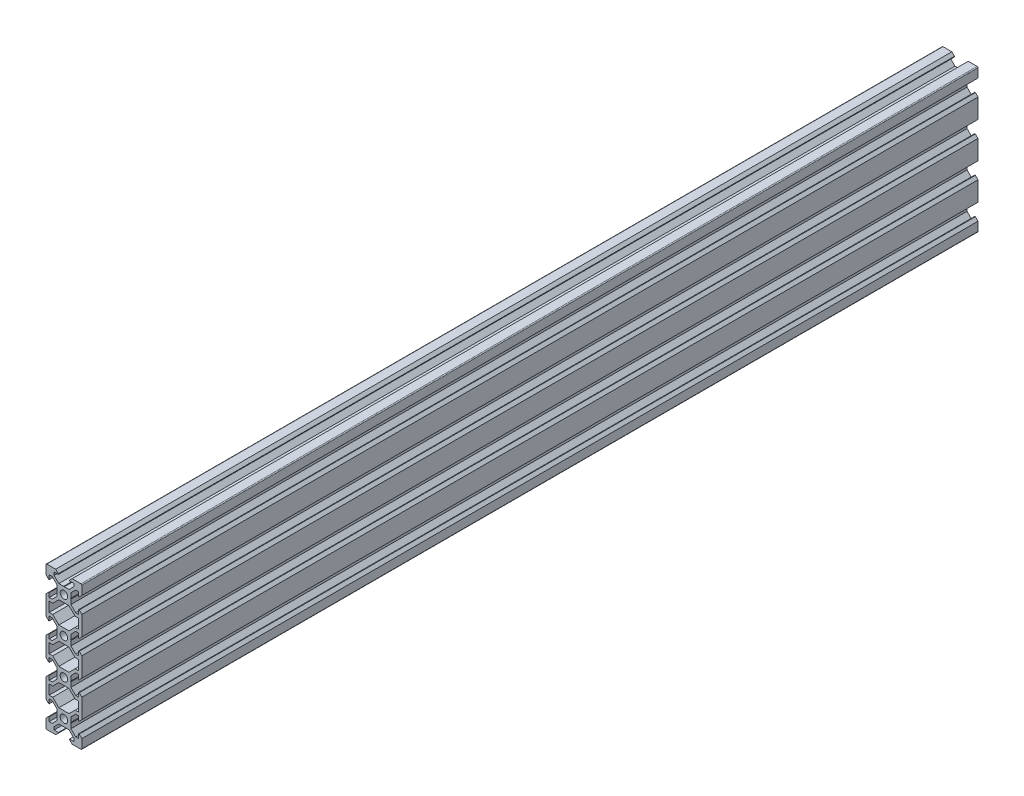
SolidWorks part; units mm, degrees
material "6061-T6 (SS)"
ref_plane "Front Plane" through (0, 0, 0) normal (0, 0, 1) x (1, 0, 0)
ref_plane "Top Plane" through (0, 0, 0) normal (0, 1, 0) x (1, 0, 0)
ref_plane "Right Plane" through (0, 0, 0) normal (1, 0, 0) x (0, 0, -1)
sketch "Sketch1" plane through (0, 0, 0) normal (0, 0, 1) x (1, 0, 0)
  line L0 (0, 0) -> (10, 0) construction
  line L1 (9.5, -40) -> (-9.5, -40)
  line L2 (10, -39.5) -> (10, 39.5)
  line L3 (9.5, 40) -> (-9.5, 40)
  line L4 (-10, -39.5) -> (-10, 39.5)
  line L5 (10, -40) -> (-10, 40) construction
  line L6 (10, 40) -> (-10, -40) construction
  circle A0 centre (0, 30) radius 2.1
  circle A1 centre (0, 10) radius 2.1
  circle A2 centre (0, -10) radius 2.1
  circle A3 centre (0, -30) radius 2.1
  arc A4 (-9.5, -40) -> (-10, -39.5) centre (-9.5, -39.5) cw
  arc A5 (9.5, -40) -> (10, -39.5) centre (9.5, -39.5) ccw
  arc A6 (10, 39.5) -> (9.5, 40) centre (9.5, 39.5) ccw
  arc A7 (-9.5, 40) -> (-10, 39.5) centre (-9.5, 39.5) ccw
  point P0 (0, 0)
  line B0 (0, 30) -> (0, 40) construction
  line B1 (0, 33.69) -> (-0.21, 33.9)
  line B2 (-0.21, 33.9) -> (-2.8393, 33.9)
  line B3 (-2.8393, 33.9) -> (-5.5, 36.5607)
  line B4 (-5.5, 36.5607) -> (-5.5, 38.2)
  line B5 (-5.5, 38.2) -> (-3.125, 38.2)
  line B6 (-3.125, 38.2) -> (-3.125, 38.545)
  line B7 (-3.125, 38.545) -> (-4.58, 40)
  line B8 (-4.58, 40) -> (4.58, 40)
  line B9 (0, 30) -> (-5.9132, 35.9132) construction
  line B10 (3.125, 38.545) -> (4.58, 40)
  line B11 (3.125, 38.2) -> (3.125, 38.545)
  line B12 (5.5, 38.2) -> (3.125, 38.2)
  line B13 (5.5, 36.5607) -> (5.5, 38.2)
  line B14 (2.8393, 33.9) -> (5.5, 36.5607)
  line B15 (0.21, 33.9) -> (2.8393, 33.9)
  line B16 (0, 33.69) -> (0.21, 33.9)
  line B17 (0, 30) -> (-10, 30) construction
  line B18 (-3.69, 30) -> (-3.9, 29.79)
  line B19 (-3.9, 29.79) -> (-3.9, 27.1607)
  line B20 (-3.9, 27.1607) -> (-6.5607, 24.5)
  line B21 (-6.5607, 24.5) -> (-8.2, 24.5)
  line B22 (-8.2, 24.5) -> (-8.2, 26.875)
  line B23 (-8.2, 26.875) -> (-8.545, 26.875)
  line B24 (-8.545, 26.875) -> (-10, 25.42)
  line B25 (-10, 25.42) -> (-10, 34.58)
  line B26 (0, 30) -> (-5.9132, 24.0868) construction
  line B27 (-8.545, 33.125) -> (-10, 34.58)
  line B28 (-8.2, 33.125) -> (-8.545, 33.125)
  line B29 (-8.2, 35.5) -> (-8.2, 33.125)
  line B30 (-6.5607, 35.5) -> (-8.2, 35.5)
  line B31 (-3.9, 32.8393) -> (-6.5607, 35.5)
  line B32 (-3.9, 30.21) -> (-3.9, 32.8393)
  line B33 (-3.69, 30) -> (-3.9, 30.21)
  line B34 (0, 10) -> (-10, 10) construction
  line B35 (-3.69, 10) -> (-3.9, 9.79)
  line B36 (-3.9, 9.79) -> (-3.9, 7.1607)
  line B37 (-3.9, 7.1607) -> (-6.5607, 4.5)
  line B38 (-6.5607, 4.5) -> (-8.2, 4.5)
  line B39 (-8.2, 4.5) -> (-8.2, 6.875)
  line B40 (-8.2, 6.875) -> (-8.545, 6.875)
  line B41 (-8.545, 6.875) -> (-10, 5.42)
  line B42 (-10, 5.42) -> (-10, 14.58)
  line B43 (0, 10) -> (-5.9132, 4.0868) construction
  line B44 (-8.545, 13.125) -> (-10, 14.58)
  line B45 (-8.2, 13.125) -> (-8.545, 13.125)
  line B46 (-8.2, 15.5) -> (-8.2, 13.125)
  line B47 (-6.5607, 15.5) -> (-8.2, 15.5)
  line B48 (-3.9, 12.8393) -> (-6.5607, 15.5)
  line B49 (-3.9, 10.21) -> (-3.9, 12.8393)
  line B50 (-3.69, 10) -> (-3.9, 10.21)
  line B51 (0, -10) -> (-10, -10) construction
  line B52 (-3.69, -10) -> (-3.9, -10.21)
  line B53 (-3.9, -10.21) -> (-3.9, -12.8393)
  line B54 (-3.9, -12.8393) -> (-6.5607, -15.5)
  line B55 (-6.5607, -15.5) -> (-8.2, -15.5)
  line B56 (-8.2, -15.5) -> (-8.2, -13.125)
  line B57 (-8.2, -13.125) -> (-8.545, -13.125)
  line B58 (-8.545, -13.125) -> (-10, -14.58)
  line B59 (-10, -14.58) -> (-10, -5.42)
  line B60 (0, -10) -> (-5.9132, -15.9132) construction
  line B61 (-8.545, -6.875) -> (-10, -5.42)
  line B62 (-8.2, -6.875) -> (-8.545, -6.875)
  line B63 (-8.2, -4.5) -> (-8.2, -6.875)
  line B64 (-6.5607, -4.5) -> (-8.2, -4.5)
  line B65 (-3.9, -7.1607) -> (-6.5607, -4.5)
  line B66 (-3.9, -9.79) -> (-3.9, -7.1607)
  line B67 (-3.69, -10) -> (-3.9, -9.79)
  line B68 (0, -30) -> (-10, -30) construction
  line B69 (-3.69, -30) -> (-3.9, -30.21)
  line B70 (-3.9, -30.21) -> (-3.9, -32.8393)
  line B71 (-3.9, -32.8393) -> (-6.5607, -35.5)
  line B72 (-6.5607, -35.5) -> (-8.2, -35.5)
  line B73 (-8.2, -35.5) -> (-8.2, -33.125)
  line B74 (-8.2, -33.125) -> (-8.545, -33.125)
  line B75 (-8.545, -33.125) -> (-10, -34.58)
  line B76 (-10, -34.58) -> (-10, -25.42)
  line B77 (0, -30) -> (-5.9132, -35.9132) construction
  line B78 (-8.545, -26.875) -> (-10, -25.42)
  line B79 (-8.2, -26.875) -> (-8.545, -26.875)
  line B80 (-8.2, -24.5) -> (-8.2, -26.875)
  line B81 (-6.5607, -24.5) -> (-8.2, -24.5)
  line B82 (-3.9, -27.1607) -> (-6.5607, -24.5)
  line B83 (-3.9, -29.79) -> (-3.9, -27.1607)
  line B84 (-3.69, -30) -> (-3.9, -29.79)
  line B85 (0, -30) -> (0, -40) construction
  line B86 (0, -33.69) -> (0.21, -33.9)
  line B87 (0.21, -33.9) -> (2.8393, -33.9)
  line B88 (2.8393, -33.9) -> (5.5, -36.5607)
  line B89 (5.5, -36.5607) -> (5.5, -38.2)
  line B90 (5.5, -38.2) -> (3.125, -38.2)
  line B91 (3.125, -38.2) -> (3.125, -38.545)
  line B92 (3.125, -38.545) -> (4.58, -40)
  line B93 (4.58, -40) -> (-4.58, -40)
  line B94 (0, -30) -> (5.9132, -35.9132) construction
  line B95 (-3.125, -38.545) -> (-4.58, -40)
  line B96 (-3.125, -38.2) -> (-3.125, -38.545)
  line B97 (-5.5, -38.2) -> (-3.125, -38.2)
  line B98 (-5.5, -36.5607) -> (-5.5, -38.2)
  line B99 (-2.8393, -33.9) -> (-5.5, -36.5607)
  line B100 (-0.21, -33.9) -> (-2.8393, -33.9)
  line B101 (0, -33.69) -> (-0.21, -33.9)
  line B102 (0, -30) -> (10, -30) construction
  line B103 (3.69, -30) -> (3.9, -29.79)
  line B104 (3.9, -29.79) -> (3.9, -27.1607)
  line B105 (3.9, -27.1607) -> (6.5607, -24.5)
  line B106 (6.5607, -24.5) -> (8.2, -24.5)
  line B107 (8.2, -24.5) -> (8.2, -26.875)
  line B108 (8.2, -26.875) -> (8.545, -26.875)
  line B109 (8.545, -26.875) -> (10, -25.42)
  line B110 (10, -25.42) -> (10, -34.58)
  line B111 (0, -30) -> (5.9132, -24.0868) construction
  line B112 (8.545, -33.125) -> (10, -34.58)
  line B113 (8.2, -33.125) -> (8.545, -33.125)
  line B114 (8.2, -35.5) -> (8.2, -33.125)
  line B115 (6.5607, -35.5) -> (8.2, -35.5)
  line B116 (3.9, -32.8393) -> (6.5607, -35.5)
  line B117 (3.9, -30.21) -> (3.9, -32.8393)
  line B118 (3.69, -30) -> (3.9, -30.21)
  line B119 (0, -10) -> (10, -10) construction
  line B120 (3.69, -10) -> (3.9, -9.79)
  line B121 (3.9, -9.79) -> (3.9, -7.1607)
  line B122 (3.9, -7.1607) -> (6.5607, -4.5)
  line B123 (6.5607, -4.5) -> (8.2, -4.5)
  line B124 (8.2, -4.5) -> (8.2, -6.875)
  line B125 (8.2, -6.875) -> (8.545, -6.875)
  line B126 (8.545, -6.875) -> (10, -5.42)
  line B127 (10, -5.42) -> (10, -14.58)
  line B128 (0, -10) -> (5.9132, -4.0868) construction
  line B129 (8.545, -13.125) -> (10, -14.58)
  line B130 (8.2, -13.125) -> (8.545, -13.125)
  line B131 (8.2, -15.5) -> (8.2, -13.125)
  line B132 (6.5607, -15.5) -> (8.2, -15.5)
  line B133 (3.9, -12.8393) -> (6.5607, -15.5)
  line B134 (3.9, -10.21) -> (3.9, -12.8393)
  line B135 (3.69, -10) -> (3.9, -10.21)
  line B136 (0, 10) -> (10, 10) construction
  line B137 (3.69, 10) -> (3.9, 10.21)
  line B138 (3.9, 10.21) -> (3.9, 12.8393)
  line B139 (3.9, 12.8393) -> (6.5607, 15.5)
  line B140 (6.5607, 15.5) -> (8.2, 15.5)
  line B141 (8.2, 15.5) -> (8.2, 13.125)
  line B142 (8.2, 13.125) -> (8.545, 13.125)
  line B143 (8.545, 13.125) -> (10, 14.58)
  line B144 (10, 14.58) -> (10, 5.42)
  line B145 (0, 10) -> (5.9132, 15.9132) construction
  line B146 (8.545, 6.875) -> (10, 5.42)
  line B147 (8.2, 6.875) -> (8.545, 6.875)
  line B148 (8.2, 4.5) -> (8.2, 6.875)
  line B149 (6.5607, 4.5) -> (8.2, 4.5)
  line B150 (3.9, 7.1607) -> (6.5607, 4.5)
  line B151 (3.9, 9.79) -> (3.9, 7.1607)
  line B152 (3.69, 10) -> (3.9, 9.79)
  line B153 (0, 30) -> (10, 30) construction
  line B154 (3.69, 30) -> (3.9, 30.21)
  line B155 (3.9, 30.21) -> (3.9, 32.8393)
  line B156 (3.9, 32.8393) -> (6.5607, 35.5)
  line B157 (6.5607, 35.5) -> (8.2, 35.5)
  line B158 (8.2, 35.5) -> (8.2, 33.125)
  line B159 (8.2, 33.125) -> (8.545, 33.125)
  line B160 (8.545, 33.125) -> (10, 34.58)
  line B161 (10, 34.58) -> (10, 25.42)
  line B162 (0, 30) -> (5.9132, 35.9132) construction
  line B163 (8.545, 26.875) -> (10, 25.42)
  line B164 (8.2, 26.875) -> (8.545, 26.875)
  line B165 (8.2, 24.5) -> (8.2, 26.875)
  line B166 (6.5607, 24.5) -> (8.2, 24.5)
  line B167 (3.9, 27.1607) -> (6.5607, 24.5)
  line B168 (3.9, 29.79) -> (3.9, 27.1607)
  line B169 (3.69, 30) -> (3.9, 29.79)
  line B170 (-8.2, 17.3) -> (-8.2, 22.7)
  line B171 (-8.2, 22.7) -> (-6.2393, 22.7)
  line B172 (-6.2393, 22.7) -> (-2.8393, 26.1)
  line B173 (-2.8393, 26.1) -> (2.8393, 26.1)
  line B174 (0, 26.1) -> (0, 20) construction
  line B175 (0, 20) -> (-8.2, 20) construction
  line B176 (6.2393, 22.7) -> (2.8393, 26.1)
  line B177 (8.2, 22.7) -> (6.2393, 22.7)
  line B178 (8.2, 17.3) -> (8.2, 22.7)
  line B179 (8.2, 17.3) -> (6.2393, 17.3)
  line B180 (6.2393, 17.3) -> (2.8393, 13.9)
  line B181 (-2.8393, 13.9) -> (2.8393, 13.9)
  line B182 (-6.2393, 17.3) -> (-2.8393, 13.9)
  line B183 (-8.2, 17.3) -> (-6.2393, 17.3)
  line B184 (0, 26.1) -> (0, 30) construction
  line B185 (0, 30) -> (-5.0927, 24.9073) construction
  line B186 (-8.2, -2.7) -> (-8.2, 2.7)
  line B187 (-8.2, 2.7) -> (-6.2393, 2.7)
  line B188 (-6.2393, 2.7) -> (-2.8393, 6.1)
  line B189 (-2.8393, 6.1) -> (2.8393, 6.1)
  line B190 (0, 6.1) -> (0, 0) construction
  line B191 (0, 0) -> (-8.2, 0) construction
  line B192 (6.2393, 2.7) -> (2.8393, 6.1)
  line B193 (8.2, 2.7) -> (6.2393, 2.7)
  line B194 (8.2, -2.7) -> (8.2, 2.7)
  line B195 (8.2, -2.7) -> (6.2393, -2.7)
  line B196 (6.2393, -2.7) -> (2.8393, -6.1)
  line B197 (-2.8393, -6.1) -> (2.8393, -6.1)
  line B198 (-6.2393, -2.7) -> (-2.8393, -6.1)
  line B199 (-8.2, -2.7) -> (-6.2393, -2.7)
  line B200 (0, 6.1) -> (0, 10) construction
  line B201 (0, 10) -> (-5.0927, 4.9073) construction
  line B202 (-8.2, -22.7) -> (-8.2, -17.3)
  line B203 (-8.2, -17.3) -> (-6.2393, -17.3)
  line B204 (-6.2393, -17.3) -> (-2.8393, -13.9)
  line B205 (-2.8393, -13.9) -> (2.8393, -13.9)
  line B206 (0, -13.9) -> (0, -20) construction
  line B207 (0, -20) -> (-8.2, -20) construction
  line B208 (6.2393, -17.3) -> (2.8393, -13.9)
  line B209 (8.2, -17.3) -> (6.2393, -17.3)
  line B210 (8.2, -22.7) -> (8.2, -17.3)
  line B211 (8.2, -22.7) -> (6.2393, -22.7)
  line B212 (6.2393, -22.7) -> (2.8393, -26.1)
  line B213 (-2.8393, -26.1) -> (2.8393, -26.1)
  line B214 (-6.2393, -22.7) -> (-2.8393, -26.1)
  line B215 (-8.2, -22.7) -> (-6.2393, -22.7)
  line B216 (0, -13.9) -> (0, -10) construction
  line B217 (0, -10) -> (-5.0927, -15.0927) construction
  dimension "D5" = 4.2
  dimension "D6" = 0.5
  dimension "D1" = 20
  dimension "D2" = 80
  dimension "D3" = 20
  dimension "D4" = 20
sketch_block_instance "V Slot 1-4"
sketch_block "V Slot 1" parameters "D1"=10, "D2"=11, "D3"=4.3, "D4"=1.8, "D5"=0.21, "D6"=45, "D7"=9.16, "D8"=1.5, "D9"=6.25
sketch_block_instance "V Slot 1-5"
sketch_block_instance "V Slot 1-6"
sketch_block_instance "V Slot 1-7"
sketch_block_instance "V Slot 1-8"
sketch_block_instance "V Slot 1-9"
sketch_block_instance "V Slot 1-10"
sketch_block_instance "V Slot 1-11"
sketch_block_instance "V Slot 1-12"
sketch_block_instance "V Slot 1-13"
sketch_block_instance "Center Cutout 1-1"
sketch_block "Center Cutout 1" parameters "D1"=5.4, "D2"=12.2, "D3"=8.2, "D4"=45, "D5"=10, "D6"=1.5
sketch_block_instance "Center Cutout 1-2"
sketch_block_instance "Center Cutout 1-3"
extrude "Boss-Extrude1" add sketch "Sketch1" along normal blind 500 contours B169 B154 B155 B156 B157 B158 B159 B160 L2 A6 L3 B10 B11 B12 B13 B14 B15 B16 B1 B2 B3 B4 B5 B6 B7 A7 L4 B27 B28 B29 B30 B31 B32 B33 B18 B19 B20 B21 B22 B23 B24 B44 B45 B46 B47 B48 B49 B50 B35 region at (7.04, -39.1754, 0)
